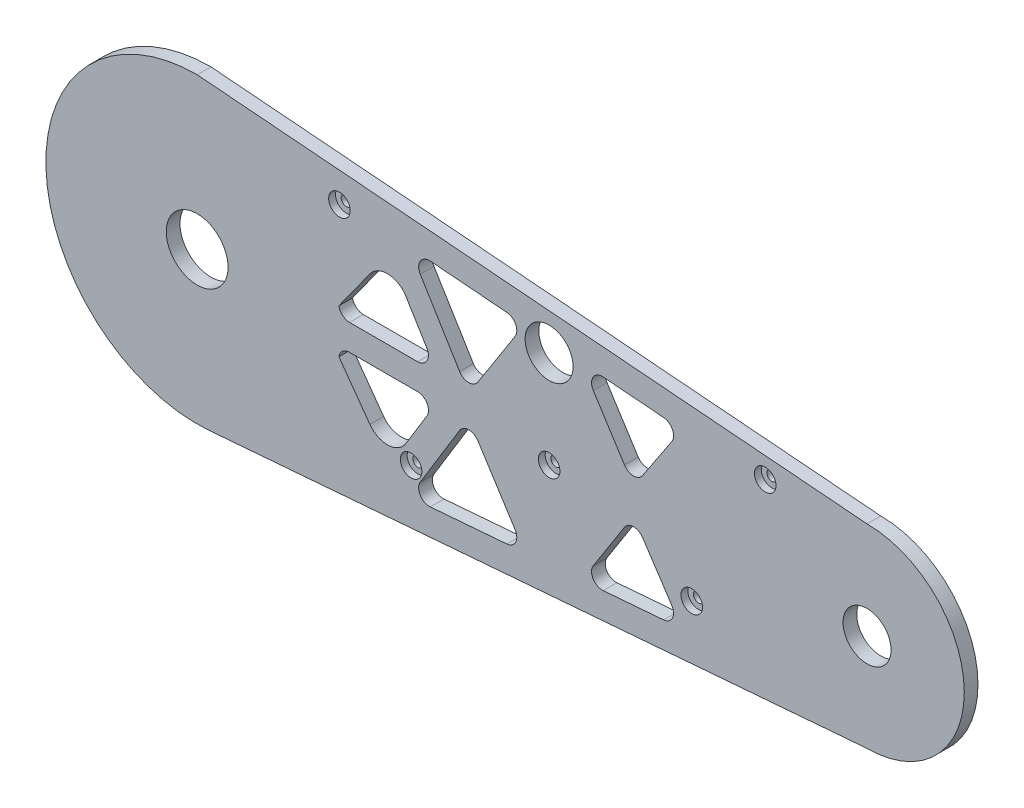
SolidWorks part; units mm, degrees
other "Marca1"
sketch "Croquis3" plane through (-70, -70, 6.35) normal (0, 0, 1) x (1, 0, 0)
material "6061-O (SS)"
ref_plane "Front Plane" through (0, 0, 0) normal (0, 0, 1) x (1, 0, 0)
ref_plane "Top Plane" through (0, 0, 0) normal (0, 1, 0) x (1, 0, 0)
ref_plane "Right Plane" through (0, 0, 0) normal (1, 0, 0) x (0, 0, -1)
sketch "Sketch1" plane through (0, 0, 0) normal (0, 0, 1) x (1, 0, 0)
  line L0 (0, 70) -> (310, 45)
  line L1 (5.1714, -69.8087) -> (310, -45)
  line L2 (0, 0) -> (310, 0) construction
  line L3 (107.899, 49.2595) -> (143.3142, 46.4034)
  line L4 (70.5232, 6) -> (102.03, 6)
  line L5 (219.6238, 32.8105) -> (206.1309, 12.4175)
  line L6 (197.7459, 12.4871) -> (183.2969, 35.1335)
  line L7 (162.8785, 6) -> (162.8785, -6) construction
  line L8 (258.6323, 64.5867) -> (258.6323, 39.5867) construction
  line L9 (147.1275, 38.7303) -> (129.9162, 11.7546)
  line L10 (121.433, 11.8395) -> (103.229, 41.6712)
  line L11 (98.117, 50.0484) -> (42.0027, 50.0484) construction
  line L12 (187.9139, 42.8067) -> (215.8558, 40.5533)
  line L13 (162.8785, 44.8257) -> (162.8785, 6) construction
  line L14 (67.1248, 64.5867) -> (162.8785, 40) construction
  line L15 (201.8849, 6) -> (201.8849, 41.68) construction
  line L16 (125.6066, 5) -> (125.6066, 47.8315) construction
  line L17 (96.5904, 29.5131) -> (106.2981, 13.6045)
  line L18 (125.6066, -5) -> (125.6066, -47.8315) construction
  line L19 (201.8849, -6) -> (201.8849, -41.68) construction
  line L20 (162.8785, -44.8257) -> (162.8785, -6) construction
  line L21 (98.117, -50.0484) -> (42.0027, -50.0484) construction
  line L22 (96.5904, -29.5131) -> (106.2981, -13.6045)
  line L23 (67.1248, 64.5867) -> (409.6974, 64.5867) construction
  line L24 (187.9139, -42.8067) -> (215.8558, -40.5533)
  line L25 (121.433, -11.8395) -> (103.229, -41.6712)
  line L26 (147.1275, -38.7303) -> (129.9162, -11.7546)
  line L27 (162.8785, 0) -> (258.6323, 64.5867) construction
  line L28 (67.1248, 64.5867) -> (67.1248, 39.5867) construction
  line L29 (197.7459, -12.4871) -> (183.2969, -35.1335)
  line L30 (219.6238, -32.8105) -> (206.1309, -12.4175)
  line L31 (70.5232, -6) -> (102.03, -6)
  line L32 (107.899, -49.2595) -> (143.3142, -46.4034)
  line L33 (0, -6.35) -> (0, 6.35) construction
  line L34 (67.1248, 39.5867) -> (162.8785, 40) construction
  line L35 (162.8785, 40) -> (68.3705, 24.1395) construction
  line L36 (79.9417, 30.1512) -> (65.583, 10.2294)
  line L37 (79.9417, -30.1512) -> (65.583, -10.2294)
  arc A0 (65.583, 10.2294) -> (70.5232, 6) centre (70.5232, 11) ccw
  arc A1 (310, -45) -> (310, 45) centre (310, 0) ccw
  circle A2 centre (0, 0) radius 14.2938
  circle A3 centre (310, 0) radius 11.116
  arc A4 (79.9417, 30.1512) -> (96.5904, 29.5131) centre (88.0542, 24.3041) cw
  arc A5 (79.9417, -30.1512) -> (96.5904, -29.5131) centre (88.0542, -24.3041) ccw
  arc A6 (0, 70) -> (5.1714, -69.8087) centre (0, 0) ccw
  arc A7 (187.9139, 42.8067) -> (183.2969, 35.1335) centre (187.512, 37.8229) ccw
  arc A8 (219.6238, 32.8105) -> (215.8558, 40.5533) centre (215.4539, 35.5695) ccw
  arc A9 (206.1309, 12.4175) -> (197.7459, 12.4871) centre (201.961, 15.1765) cw
  circle A10 centre (162.8785, 40) radius 11.1125
  arc A13 (102.03, 6) -> (106.2981, 13.6045) centre (102.03, 11) ccw
  arc A14 (121.433, 11.8395) -> (129.9162, 11.7546) centre (125.7011, 14.444) ccw
  arc A15 (147.1275, 38.7303) -> (143.3142, 46.4034) centre (142.9123, 41.4196) ccw
  arc A16 (107.899, 49.2595) -> (103.229, 41.6712) centre (107.4971, 44.2757) ccw
  arc A17 (107.899, -49.2595) -> (103.229, -41.6712) centre (107.4971, -44.2757) cw
  arc A18 (147.1275, -38.7303) -> (143.3142, -46.4034) centre (142.9123, -41.4196) cw
  arc A19 (121.433, -11.8395) -> (129.9162, -11.7546) centre (125.7011, -14.444) cw
  arc A20 (102.03, -6) -> (106.2981, -13.6045) centre (102.03, -11) cw
  arc A24 (206.1309, -12.4175) -> (197.7459, -12.4871) centre (201.961, -15.1765) ccw
  arc A25 (219.6238, -32.8105) -> (215.8558, -40.5533) centre (215.4539, -35.5695) cw
  arc A26 (187.9139, -42.8067) -> (183.2969, -35.1335) centre (187.512, -37.8229) cw
  arc A29 (65.583, -10.2294) -> (70.5232, -6) centre (70.5232, -11) cw
  point P31 (177.8851, 43.6155)
  point P42 (187.6504, 6)
  point P44 (88.7465, 42.3671)
  point P45 (138.1067, 6)
  point P79 (88.7465, -42.3671)
  point P100 (138.1067, -6)
  point P101 (187.6504, -6)
  point P102 (177.8851, -43.6155)
  point P104 (0, 0)
  point P114 (310, 0)
  point P119 (0.2114, 0.3175)
  dimension "D2" = 45
  dimension "D3" = 12.7
  dimension "D4" = 22.232
  dimension "D6" = 12
  dimension "D11" = 5
  dimension "D12" = 70
  dimension "D13" = 25
  dimension "D8" = 5
  dimension "D14" = 12
  dimension "D15" = 25
  dimension "D16" = 310
  dimension "D17" = 22.225
  dimension "D5" = 28.5877
  dimension "D19" = 10
  dimension "D20" = 10
  dimension "D7" = 6
  dimension "D9" = 9.279
  dimension "D10" = 34
  dimension "D18" = 40
extrude "Boss-Extrude1" add sketch "Sketch1" along normal blind 6.35
sketch "Sketch2" plane through (0, 0, 6.35) normal (0, 0, 1) x (1, 0, 0)
  line L0 (263.0927, 39.4927) -> (-0.4655, 64.9983)
  line L1 (4.6885, -64.8307) -> (263.1366, -39.5384)
  arc A0 (-0.4655, 64.9983) -> (4.6885, -64.8307) centre (0, 0) ccw
  arc A1 (263.1366, -39.5384) -> (270.3186, -23.7999) centre (262.1626, -29.5859) ccw
  circle A2 centre (0, 0) radius 40
  arc A3 (270.292, 23.7623) -> (270.3186, -23.7999) centre (303.867, 0) ccw
  arc A4 (270.292, 23.7623) -> (263.0927, 39.4927) centre (262.1295, 29.5392) ccw
  dimension "D1" = 10
  dimension "D2" = 41.133
  dimension "D3" = 65
ref_plane "Plane1" through (0, 0, 10) normal (0, 0, 1) x (1, 0, 0)
sketch "Croquis1" plane through (0, 0, 6.35) normal (0, 0, 1) x (1, 0, 0)
  circle A1 centre (98.9956, -37.0901) radius 2.3813
  circle A2 centre (228.8774, -26.5196) radius 2.3813
  point P20 (0, 0)
  dimension "D5" = 4.7625
  dimension "D1" = 4.7625
extrude "Cortar-Extruir1" cut sketch "Croquis1" against normal blind 50
sketch "Croquis4" plane through (0, 0, 0) normal (0, 0, -1) x (-1, 0, 0)
  circle A0 centre (-228.8774, -26.5196) radius 5
  circle A1 centre (-98.9956, -37.0901) radius 5
  dimension "D1" = 10
sketch "Croquis5" plane through (0, 0, 0) normal (0, 0, -1) x (-1, 0, 0)
  line L0 (-162.8785, 40) -> (-162.8785, -35.6506) construction
  line L1 (-193.2674, -35.6506) -> (-132.4897, -35.6506) construction
  circle A0 centre (-162.8785, 0) radius 5
  point P6 (-162.8785, -35.6506)
  dimension "D2" = 10
  dimension "D1" = 40
sketch "Croquis6" plane through (0, 0, 0) normal (0, 0, -1) x (-1, 0, 0)
  circle A0 centre (-162.8785, -5) radius 2.3813
  dimension "D1" = 4.7625
extrude "Cortar-Extruir4" cut sketch "Croquis6" against normal blind 10
sketch "Croquis7" plane through (0, 0, 0) normal (0, 0, -1) x (-1, 0, 0)
  line L0 (-228.8774, -26.5196) -> (-98.9956, -37.0901) construction
  line L1 (-98.9956, -37.0901) -> (-65.8414, 50.869) construction
  line L2 (-228.8774, -26.5196) -> (-262.8716, 39.2101) construction
  circle A0 centre (-65.8414, 50.869) radius 2.3813
  circle A1 centre (-262.8716, 39.2101) radius 2.3813
  dimension "D5" = 4.7625
  dimension "D1" = 94
  dimension "D2" = 106
  dimension "D3" = 74
  dimension "D4" = 238
extrude "Cortar-Extruir5" cut sketch "Croquis7" against normal blind 10
sketch "Croquis8" plane through (0, 0, 0) normal (0, 0, -1) x (-1, 0, 0)
  circle A0 centre (-262.8716, 39.2101) radius 5
  circle A1 centre (-65.8414, 50.869) radius 5
  dimension "D1" = 10
  dimension "D2" = 10
sketch "Croquis9" plane through (0, 0, 6.35) normal (0, 0, 1) x (1, 0, 0)
  circle A0 centre (65.8414, 50.869) radius 5
  circle A1 centre (162.8785, -5) radius 5
  circle A2 centre (98.9956, -37.0901) radius 5
  circle A3 centre (228.8774, -26.5196) radius 5
  circle A4 centre (262.8716, 39.2101) radius 5
  dimension "D1" = 10
extrude "Cortar-Extruir6" cut sketch "Croquis9" against normal blind 3.18
